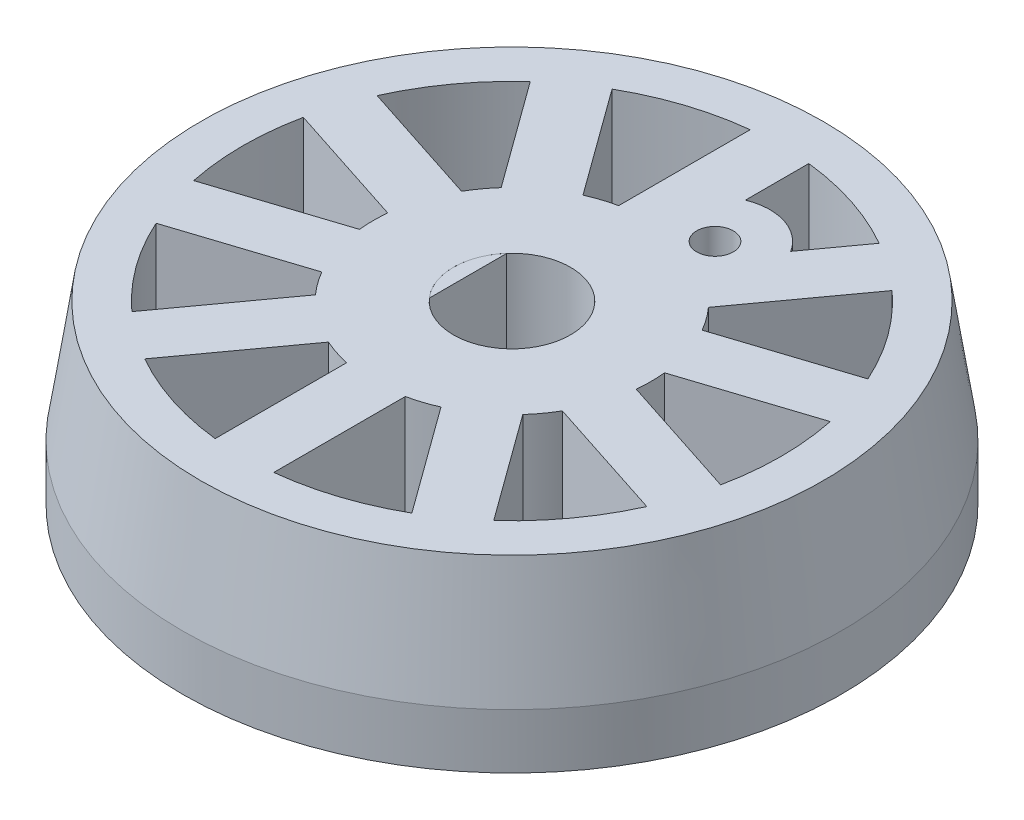
SolidWorks part; units mm, degrees
other "标注1"
sketch "草图3" plane through (-22.25, 4, -10) normal (-0.231, 0.6469, -0.7268) x (-0.9696, -0.2151, 0.1167)
ref_plane "前视基准面" through (0, 0, 0) normal (0, 0, 1) x (1, 0, 0)
ref_plane "上视基准面" through (0, 0, 0) normal (0, 1, 0) x (1, 0, 0)
ref_plane "右视基准面" through (0, 0, 0) normal (1, 0, 0) x (0, 0, -1)
other "Configuration Table"
sketch "草图4" plane through (0, 0, 0) normal (0, 1, 0) x (1, 0, 0)
  line L0 (-1.2, 1.0583) -> (-1.2, -1.0583)
  circle A0 centre (0, 0) radius 11.6
  circle A1 centre (0, 0) radius 1.6
  circle A2 centre (0, 0) radius 9
  dimension "D1" = 23.2
  dimension "D2" = 3.2
  dimension "D3" = 18
  dimension "D4" = 1.2
extrude "凸台-拉伸1" add sketch "草图4" along normal blind 1.1 contours A0 | A1
extrude "凸台-拉伸2" add sketch "草图4<3>" along normal blind 3.3 from offset 1.5 contours A2 | A1
sketch "草图4<3>" plane through (0, 0, 0) normal (0, 1, 0) x (1, 0, 0) same geometry as "草图4"
chamfer "倒角1" distance 0.2 angle 45 1 edges at (0, 1.1, 11.6)
loft "放样1" add section edge at (0, 1.5, 9) section edge at (0, 1.1, 11.4) connector at (0.6328, 1.5, 8.9777) connector at (2.6543, 1.1, 11.0867)
extrude "切除-拉伸2" cut sketch "草图4<4>" along normal through all contours A1
sketch "草图4<4>" plane through (0, 0, 0) normal (0, 1, 0) x (1, 0, 0) same geometry as "草图4"
chamfer "倒角2" distance 3.3 distance2 0.5 1 edges at (0, 4.8, 9) first distance on face at (0, 4.8, 9)
sketch "草图5" plane through (0, 4.8, 0) normal (0, 1, 0) x (1, 0, 0)
  line L0 (-0.8, 3.7148) -> (-0.8, 7.3063)
  line L1 (0, 3.8) -> (0, 7.35) construction
  line L2 (0.8, 7.3063) -> (0.8, 3.7148)
  circle A0 centre (0, 0) radius 3.8
  circle A1 centre (0, 0) radius 7.35
  dimension "D1" = 7.6
  dimension "D2" = 14.7
  dimension "D3" = 0.8
  dimension "D4" = 0.8
extrude "切除-拉伸4" cut sketch "草图5" against normal through all contours L0 A1 L2 A0 | A0 L1 A1 L0 | L1 A0 L2 A1 region at (-2.5179, 4.8, 3.1178) region at (-0.4008, 4.8, -5.5535) region at (0.4008, 4.8, -5.5535)
extrude "凸台-拉伸3" add sketch "草图5<4>" against normal up to surface (4.8 mm away) contours L1 A0 L2 A1 | A0 L1 A1 L0 region at (-0.4008, 4.8, -5.5535) region at (0.4008, 4.8, -5.5535) up to face at (0, 0, 7.35)
sketch "草图5<4>" plane through (0, 4.8, 0) normal (0, 1, 0) x (1, 0, 0) same geometry as "草图5"
pattern_circular "阵列(圆周)2" count 10 over 360 about axis through (0, 1.1, 0) along (0, -1, 0) of "凸台-拉伸3" reverse direction yes
sketch "草图6" plane through (0, 4.8, 0) normal (0, 1, 0) x (1, 0, 0)
  line L0 (0.8, 3.7148) -> (1.5363, 3.4756) construction
  line L1 (1.3597, 4.1846) -> (1.1682, 3.5952) construction
  circle A0 centre (1.3597, 4.1846) radius 0.5
  circle A1 centre (1.3597, 4.1846) radius 1.5
  dimension "D2" = 1
  dimension "D3" = 1
  dimension "D1" = 4.4
extrude "凸台-拉伸4" add sketch "草图6" against normal through all contours A1
extrude "切除-拉伸5" cut sketch "草图6<3>" against normal through all contours A0
sketch "草图6<3>" plane through (0, 4.8, 0) normal (0, 1, 0) x (1, 0, 0) same geometry as "草图6"
extrude "凸台-拉伸5" add sketch "草图4<6>" along normal up to surface (4.8 mm away) separate body contours L0 A1 region at (-1.3618, 0, 0) up to face at (1.3597, 4.8, -3.6846)
sketch "草图4<6>" plane through (0, 0, 0) normal (0, 1, 0) x (1, 0, 0) same geometry as "草图4"
sketch "草图7" plane through (0, 4.8, 0) normal (0, 1, 0) x (1, 0, 0)
  circle A0 centre (0, 0) radius 9
  circle A1 centre (0, 0) radius 9 construction
  point P3 (0, 0)
extrude "切除-拉伸6" cut sketch "草图7" against normal through all flip side to cut
